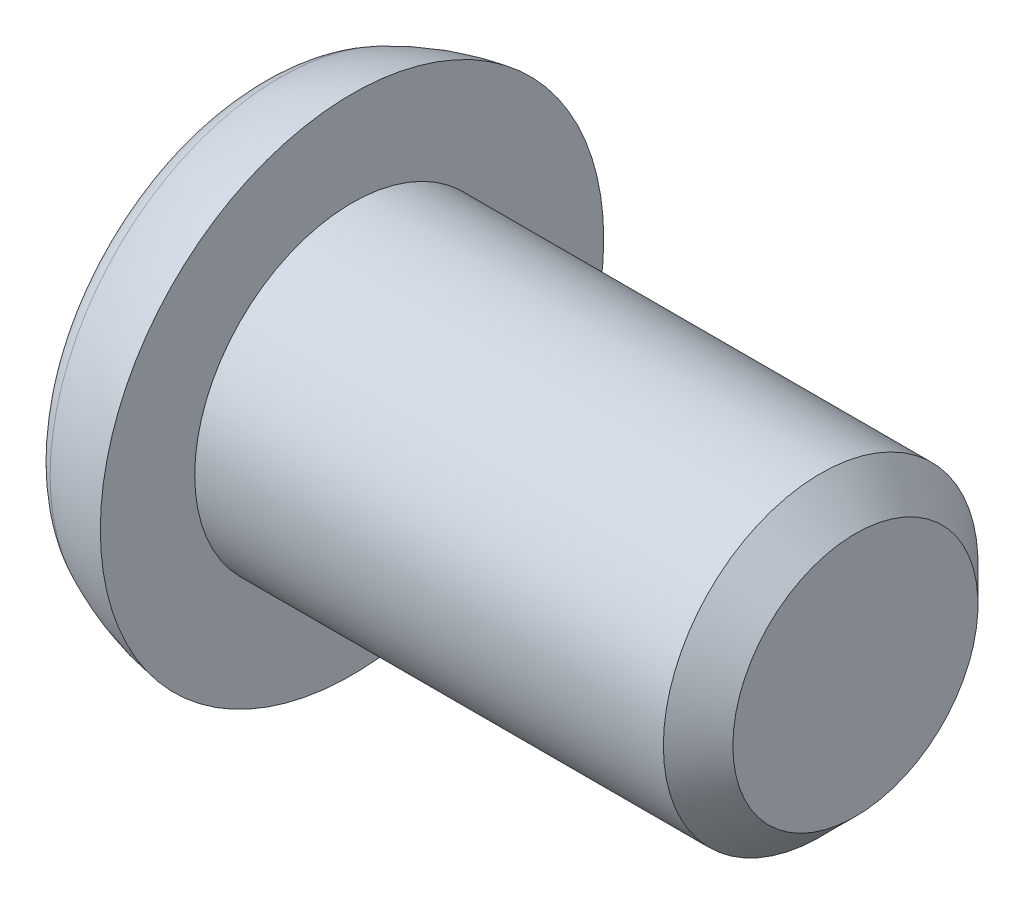
SolidWorks part; units mm, degrees
ref_plane "Front Plane" through (0, 0, 0) normal (0, 0, 1) x (1, 0, 0)
ref_plane "Top Plane" through (0, 0, 0) normal (0, 1, 0) x (1, 0, 0)
ref_plane "Right Plane" through (0, 0, 0) normal (1, 0, 0) x (0, 0, -1)
ref_plane "Plane1" through (0, 0, 0) normal (0, 0, 1) x (1, 0, 0)
sketch "Sketch1" plane through (0, 0, 0) normal (0, 0, 1) x (1, 0, 0)
  line L0 (-0.8, 0) -> (-0.8, 1.466)
  line L1 (0, 2) -> (0, 1.25)
  line L2 (0, 1.25) -> (3.724, 1.25)
  line L3 (3.724, 1.25) -> (4, 0.974)
  line L4 (4, 0.974) -> (4, 0)
  line L5 (4, 0) -> (-0.8, 0)
  line L6 (4, 0) -> (-0.8, 0) construction
  arc A0 (-0.8, 1.466) -> (-0.5715, 1.8274) centre (-0.4, 1.466) cw
  arc A1 (-0.5715, 1.8274) -> (0, 2) centre (0.286, 0.0206) cw
revolve "Revolve1" add sketch "Sketch1" angle 360 about L6 reverse direction yes
cosmetic thread "Cosmetic Thread1" parameters "D1"=3.522, "D2"=1.948
ref_plane "Plane2" through (0, 0, 0) normal (0, 0, 1) x (1, 0, 0)
sketch "Sketch2" plane through (0, 0, 0) normal (0, 0, 1) x (1, 0, 0)
  line L0 (-0.8, 1) -> (-0.8, -1)
  arc A0 (-0.8, -1) -> (0.32, 0) centre (-1.181, 0.554) ccw
  arc A1 (0.32, 0) -> (-0.8, 1) centre (-1.181, -0.554) ccw
extrude "Cut-Extrude1" cut sketch "Sketch2" against normal blind 0.2 and the other way blind 0.2
ref_plane "Plane3" through (0, 0, 0) normal (0, 1, 0) x (1, 0, 0)
sketch "Sketch3" plane through (0, 0, 0) normal (0, 1, 0) x (1, 0, 0)
  line L0 (-0.8, 1) -> (-0.8, -1)
  arc A0 (-0.8, -1) -> (0.32, 0) centre (-1.181, 0.554) ccw
  arc A1 (0.32, 0) -> (-0.8, 1) centre (-1.181, -0.554) ccw
extrude "Cut-Extrude2" cut sketch "Sketch3" against normal blind 0.2 and the other way blind 0.2
